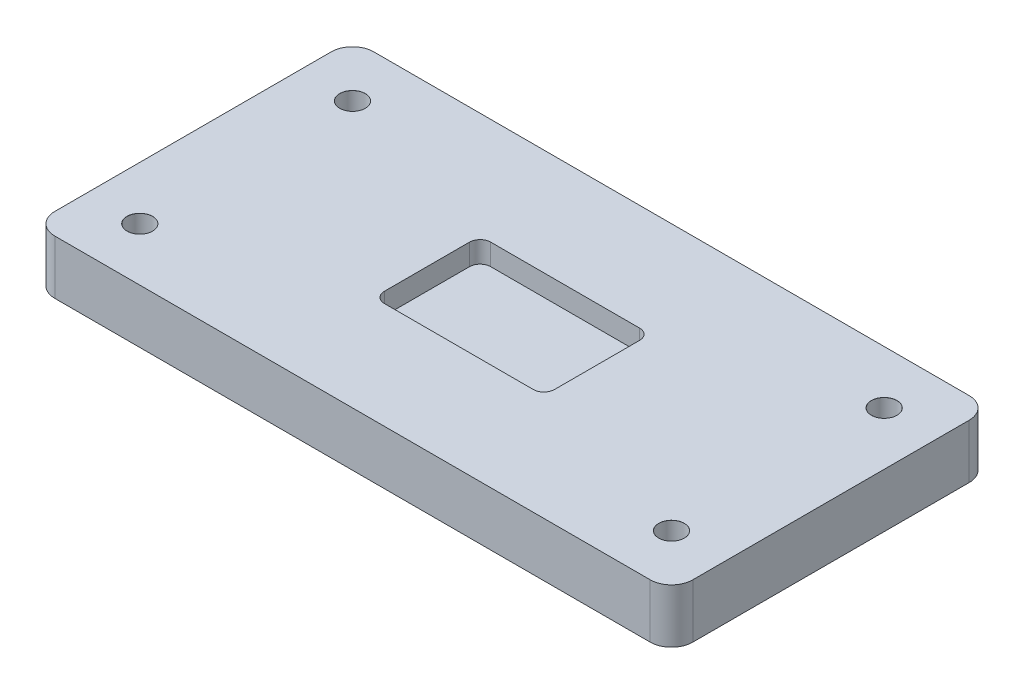
SolidWorks part; units mm, degrees
note: '?' marks a value the reader was unsure of.
ref_plane "Front Plane" through (0, 0, 0) normal (0, 0, 1) x (1, 0, 0)
ref_plane "Top Plane" through (0, 0, 0) normal (0, 1, 0) x (1, 0, 0)
ref_plane "Right Plane" through (0, 0, 0) normal (1, 0, 0) x (0, 0, -1)
ref_axis "X AXIS" through (-88.99, 0, 0) along (1, 0, 0)?
ref_axis "Y AXIS" through (0, 55, 0) along (0, -1, 0)?
ref_axis "Z AXIS" through (0, 0, -88.99) along (0, 0, 1)?
sketch "Sketch1" plane through (0, 0, 0) normal (0, 1, 0) x (1, 0, 0)
  line L1 (-140, 75) -> (140, 75)
  line L2 (-150, 65) -> (-150, -65)
  line L3 (-140, -75) -> (140, -75)
  line L4 (150, 65) -> (150, -65)
  line L5 (-150, 75) -> (150, -75) construction
  line L6 (-150, -75) -> (150, 75) construction
  arc A0 (150, 65) -> (140, 75) centre (140, 65) ccw
  arc A1 (150, -65) -> (140, -75) centre (140, -65) cw
  arc A2 (-140, -75) -> (-150, -65) centre (-140, -65) cw
  arc A3 (-150, 65) -> (-140, 75) centre (-140, 65) cw
  point P0 (0, 0)
  dimension "D3" = 10
  dimension "D1" = 300
  dimension "D2" = 150
extrude "Boss-Extrude1" add sketch "Sketch1" along normal blind 25.4
hole_wizard "CBORE for M10 Hex Head Bolt1" [suppressed] positions "Sketch2" profile "Sketch3" counterbore size "M10" standard "ANSI Metric"
sketch "Sketch2" plane through (0, 25.4, 0) normal (0, 1, 0) x (1, 0, 0)
  line L0 (0, 0) -> (0, 95.6355) construction
  line L2 (0, 0) -> (107.4622, 0) construction
  line L5 (-150, 65) -> (-150, -65) construction
  line L6 (140, 75) -> (-140, 75) construction
  point P0 (-125, 50)
  point P20 (125, 50)
  point P21 (125, -50)
  point P22 (-125, -50)
  dimension "D1" = 25
  dimension "D2" = 25
sketch "Sketch3" plane through (-125, 25.4, -50) normal (1, 0, 0) x (0, 0, 1)
  line L0 (0, 0) -> (0, 25.4)
  line L1 (0, 25.4) -> (5.5, 25.4)
  line L3 (5.5, 25.4) -> (5.5, 6.85)
  line L4 (10.74, 6.85) -> (5.5, 6.85)
  line L5 (10.74, 6.85) -> (10.74, 0.021)
  line L6 (10.74, 0.021) -> (10.765, 0)
  line L7 (10.765, 0) -> (0, 0)
  line L8 (-10.74, 0.021) -> (-10.765, 0) construction
  line L11 (0, -6.35) -> (0, 107.95) construction
  dimension "Thru Hole Dia." = 11
  dimension "Thru Hole Depth" = 25.4
  dimension "C'Bore Dia." = 21.48
  dimension "C'Bore Depth" = 6.85
  dimension "Near C'Sink Dia." = 21.53
  dimension "Near C'Sink Angle" = 100
sketch "Sketch4" plane through (0, 25.4, 0) normal (0, 1, 0) x (1, 0, 0)
  line L1 (-40, 25) -> (40, 25)
  line L2 (-40, 25) -> (-40, -25)
  line L3 (-40, -25) -> (40, -25)
  line L4 (40, 25) -> (40, -25)
  line L5 (-40, 25) -> (40, -25) construction
  line L6 (-40, -25) -> (40, 25) construction
  point P0 (0, 0)
  dimension "D1" = 80
  dimension "D2" = 50
extrude "Cut-Extrude1" cut sketch "Sketch4" against normal blind 10
fillet "Fillet1" radius 5 4 edges at (-40, 20.4, 25) (40, 20.4, 25) (-40, 20.4, -25) (40, 20.4, -25)
hole_wizard "Ø12.0 (12) Diameter Hole1" positions "Sketch5" profile "Sketch6" hole size "Ø12.0" standard "ANSI Metric" end condition through all
sketch "Sketch5" plane through (0, 25.4, 0) normal (0, 1, 0) x (1, 0, 0)
  line L0 (-150, 65) -> (-150, -65) construction
  line L1 (140, 75) -> (-140, 75) construction
  line L2 (0, 0) -> (0, 75) construction
  line L4 (0, 0) -> (150, 0) construction
  line L5 (150, -65) -> (150, 65) construction
  point P0 (-125, 50)
  point P19 (125, 50)
  point P20 (125, -50)
  point P21 (-125, -50)
  dimension "D1" = 25
  dimension "D2" = 25
sketch "Sketch6" plane through (-125, 25.4, -50) normal (1, 0, 0) x (0, 0, 1)
  line L0 (0, 0) -> (0, 25.4)
  line L1 (0, 25.4) -> (6, 25.4)
  line L2 (6, 25.4) -> (6, 0.021)
  line L3 (6, 0.021) -> (6.025, 0)
  line L5 (6.025, 0) -> (0, 0)
  line L6 (-6, 0.021) -> (-6.025, 0) construction
  line L11 (0, -6.35) -> (0, 107.95) construction
  dimension "Thru Hole Dia." = 12
  dimension "Thru Hole Depth" = 25.4
  dimension "Near C'Sink Dia." = 12.05
  dimension "Near C'Sink Angle" = 100
